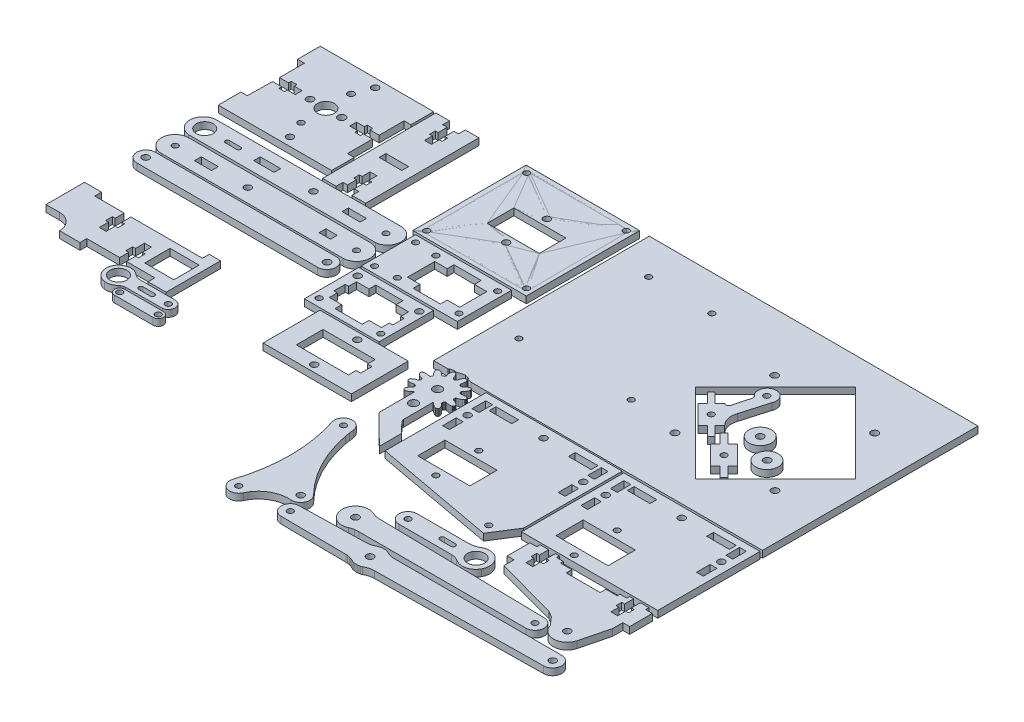
SolidWorks part; units mm, degrees
ref_plane "Front Plane" through (0, 0, 0) normal (0, 0, 1) x (1, 0, 0)
ref_plane "Top Plane" through (0, 0, 0) normal (0, 1, 0) x (1, 0, 0)
ref_plane "Right Plane" through (0, 0, 0) normal (1, 0, 0) x (0, 0, -1)
other "Graphic1"
other "Graphic (Closed) -1"
other "Graphic (Closed) -2"
other "Graphic (Closed) -3"
other "Graphic (Closed) -4"
other "Graphic (Closed) -5"
other "Graphic (Closed) -6"
other "Graphic (Closed) -7"
other "Graphic (Closed) -8"
other "Graphic (Closed) -9"
other "Graphic (Closed) -10"
other "Graphic (Closed) -11"
other "Graphic (Closed) -12"
other "Graphic (Closed) -13"
other "Graphic (Closed) -14"
other "Graphic (Closed) -15"
other "Graphic (Closed) -16"
other "Graphic (Closed) -17"
other "Graphic (Closed) -18"
other "Graphic (Closed) -19"
other "Graphic (Closed) -20"
other "Graphic (Closed) -21"
other "Graphic (Closed) -22"
other "Graphic (Closed) -23"
other "Graphic (Closed) -24"
other "Graphic (Closed) -25"
other "Graphic (Closed) -26"
other "Graphic (Closed) -27"
other "Graphic (Closed) -28"
other "Graphic (Closed) -29"
other "Graphic (Closed) -30"
other "Graphic (Closed) -31"
other "Graphic (Closed) -32"
other "Graphic (Closed) -33"
other "Graphic (Closed) -34"
other "Graphic (Closed) -35"
other "Graphic (Closed) -36"
other "Graphic (Closed) -37"
sketch "Sketch3" plane through (0, 0, 0) normal (0, 1, 0) x (1, 0, 0)
  line L0 (0, 0) -> (50, 0)
  line L1 (50, 0) -> (50, -10)
  line L2 (50, -10) -> (47, -10)
  line L3 (47, -10) -> (47, -21)
  line L4 (47, -21) -> (43, -21)
  line L5 (43, -21) -> (43, -19.8259)
  line L6 (43, -19.8259) -> (40.5, -19.75)
  line L7 (40.5, -19.75) -> (40.5, -21)
  line L8 (40.5, -21) -> (37, -21)
  line L9 (37, -21) -> (37, -24)
  line L10 (37, -24) -> (40.5, -24)
  line L11 (40.5, -24) -> (40.5, -25.275)
  line L12 (40.5, -25.275) -> (43, -25.25)
  line L13 (43, -25.25) -> (43, -24)
  line L14 (43, -24) -> (47, -24)
  line L15 (47, -24) -> (47, -35)
  line L16 (47, -35) -> (50, -35)
  line L17 (50, -35) -> (50, -45)
  line L18 (50, -45) -> (0, -45)
  line L19 (0, -45) -> (0, -35)
  line L20 (0, -35) -> (2.8271, -35)
  line L21 (3, -24) -> (7, -24)
  line L22 (7, -24) -> (7, -25.275)
  line L23 (7, -25.275) -> (9.5, -25.1741)
  line L24 (9.5, -25.1741) -> (9.5, -24)
  line L25 (9.5, -24) -> (13, -24)
  line L26 (13, -24) -> (13, -21)
  line L27 (13, -21) -> (9.5, -21)
  line L28 (9.5, -21) -> (9.5, -19.8259)
  line L29 (9.5, -19.8259) -> (7, -19.8259)
  line L30 (7, -19.8259) -> (7, -21)
  line L31 (7, -21) -> (3, -21)
  line L32 (3, -21) -> (3, -10)
  line L33 (3, -10) -> (0, -10)
  line L34 (0, -10) -> (0, 0)
  line L35 (2.8271, -35) -> (3, -24)
  circle A0 centre (25, -22.5) radius 3.75
  circle A1 centre (18, -22.5) radius 1.5333
  circle A2 centre (24.9904, -11.4176) radius 1.4239
  circle A3 centre (31.9506, -22.5119) radius 1.6482
  circle A4 centre (28, -3.75) radius 1.5
  circle A5 centre (25, -33.4941) radius 1.3524
  circle A6 centre (27.9864, -41.3394) radius 1.4891
  dimension "D1" = 10
extrude "Boss-Extrude1" add sketch "Sketch3" along normal blind 3
sketch "Sketch5" plane through (0, 0, 0) normal (0, 1, 0) x (1, 0, 0)
  line L0 (57, 0) -> (57, -3)
  line L1 (57, -3) -> (59, -3)
  line L2 (59, -3) -> (59, -7)
  line L3 (59, -7) -> (57.75, -7)
  line L4 (57.75, -7) -> (57.75, -9.5)
  line L5 (57.75, -9.5) -> (59, -9.5)
  line L6 (59, -9.5) -> (59, -13)
  line L7 (59, -13) -> (62, -13)
  line L8 (62, -13) -> (62, -9.5)
  line L9 (62, -9.5) -> (63.25, -9.5)
  line L10 (63.25, -9.5) -> (63.25, -7)
  line L11 (63.25, -7) -> (62, -7)
  line L12 (62, -7) -> (62, -3)
  line L13 (62, -3) -> (64, -3)
  line L14 (64, -3) -> (64, 0)
  line L15 (64, 0) -> (70, 0)
  line L16 (70, 0) -> (70, -50)
  line L17 (70, -50) -> (64, -50)
  line L18 (64, -50) -> (64, -47)
  line L19 (64, -47) -> (62, -47)
  line L20 (62, -47) -> (62, -43)
  line L21 (62, -43) -> (63.25, -43)
  line L22 (63.25, -43) -> (63.25, -40.5)
  line L23 (63.25, -40.5) -> (62, -40.5)
  line L24 (62, -40.5) -> (62, -37)
  line L25 (62, -37) -> (59, -37)
  line L26 (59, -37) -> (59, -40.5)
  line L27 (59, -40.5) -> (57.75, -40.5)
  line L28 (57.75, -40.5) -> (57.75, -43)
  line L29 (57.75, -43) -> (59, -43)
  line L30 (59, -43) -> (59, -47)
  line L31 (59, -47) -> (57, -47)
  line L32 (57, -47) -> (57, -50)
  line L33 (57, -50) -> (51, -50)
  line L34 (51, -50) -> (51, 0)
  line L35 (51, 0) -> (57, 0)
  line L36 (55.5, -26.5) -> (65.5, -26.5)
  line L37 (65.5, -26.5) -> (65.5, -29.5)
  line L38 (65.5, -29.5) -> (55.5, -29.5)
  line L39 (55.5, -29.5) -> (55.5, -26.5)
extrude "Boss-Extrude2" add sketch "Sketch5" along normal blind 3 separate body
sketch "Sketch8" plane through (0, 0, 0) normal (0, 1, 0) x (1, 0, 0)
  line L0 (104.5, -19.1) -> (127.5, -19.1)
  line L1 (127.5, -19.1) -> (127.5, -30.9)
  line L2 (127.5, -30.9) -> (104.5, -30.9)
  line L3 (104.5, -30.9) -> (104.5, -19.1)
  line L4 (90.8358, -0.1468) -> (90.8358, -49.9799)
  line L5 (90.8358, -49.9799) -> (140.8298, -49.9799)
  line L6 (140.8298, -49.9799) -> (140.8298, 0)
  line L7 (140.8298, 0) -> (90.8358, -0.1468)
  circle A0 centre (116, -16) radius 1.5
  circle A1 centre (116, -34) radius 1.5
  circle A2 centre (138, -3) radius 1.3
  circle A3 centre (94, -47) radius 1.3
  circle A4 centre (93.9724, -2.8702) radius 1.295
  circle A5 centre (138, -47) radius 1.3
extrude "Boss-Extrude3" add sketch "Sketch8" along normal blind 3 separate body
sketch "Sketch14" plane through (0, 0, 0) normal (0, 1, 0) x (1, 0, 0)
  line L0 (234.1407, -55.7028) -> (232.0194, -57.8241)
  line L1 (232.0194, -57.8241) -> (236.262, -62.0667)
  line L2 (236.262, -62.0667) -> (234.565, -63.7638)
  line L3 (234.565, -63.7638) -> (230.3223, -59.5211)
  line L4 (230.3223, -59.5211) -> (228.201, -61.6425)
  line L5 (228.201, -61.6425) -> (219.7157, -53.1572)
  line L6 (219.7157, -53.1572) -> (221.837, -51.0359)
  line L7 (221.837, -51.0359) -> (217.5944, -46.7932)
  line L8 (217.5944, -46.7932) -> (219.2915, -45.0962)
  line L9 (219.2915, -45.0962) -> (223.5341, -49.3388)
  line L10 (223.5341, -49.3388) -> (225.6554, -47.2175)
  line L11 (227.9135, -46.2821) -> (229.7551, -39.4354)
  line L12 (232.4436, -48.2782) -> (235.8289, -36.5593)
  line L14 (229.7551, -39.4354) -> (229.7551, -38.1986)
  line L15 (244.0402, -59.9454) -> (252.5255, -68.4307)
  line L16 (252.5255, -68.4307) -> (250.4042, -70.552)
  line L17 (250.4042, -70.552) -> (254.6468, -74.7947)
  line L18 (254.6468, -74.7947) -> (252.9497, -76.4917)
  line L19 (252.9497, -76.4917) -> (248.7071, -72.2491)
  line L20 (248.7071, -72.2491) -> (246.5858, -74.3704)
  line L21 (246.5858, -74.3704) -> (238.1005, -65.8851)
  line L22 (238.1005, -65.8851) -> (240.2218, -63.7638)
  line L23 (240.2218, -63.7638) -> (235.9792, -59.5211)
  line L24 (235.9792, -59.5211) -> (237.6762, -57.8241)
  line L25 (237.6762, -57.8241) -> (241.9189, -62.0667)
  line L26 (241.9189, -62.0667) -> (244.0402, -59.9454)
  arc A0 (225.6554, -47.2175) -> (227.9135, -46.2821) centre (226.5908, -46.2821) ccw
  arc A3 (234.1407, -55.7028) -> (232.4436, -48.2782) centre (239.2043, -50.6391) cw
  circle A4 centre (232.1046, -35.1115) radius 1.3
  arc A5 (235.8289, -36.5593) -> (229.7551, -38.1986) centre (232.1294, -34.9238) ccw
  circle A6 centre (226.9282, -54.43) radius 1.3
  circle A7 centre (246.1553, -52.0356) radius 1.55
  circle A8 centre (246.1553, -52.0356) radius 5
  circle A9 centre (256.8229, -59.6467) radius 1.55
  circle A10 centre (256.7818, -59.6877) radius 5.004
  circle A11 centre (245.313, -67.1579) radius 1.3
extrude "Boss-Extrude5" add sketch "Sketch14" along normal blind 3 separate body
sketch "Sketch10" plane through (0, 0, 0) normal (0, 1, 0) x (1, 0, 0)
  line L0 (145.1554, 0) -> (145.1554, -95.0975)
  line L1 (145.1554, -95.0975) -> (290.1997, -95.0975)
  line L2 (290.1997, -95.0975) -> (290.1997, 0)
  line L3 (290.1997, 0) -> (145.1554, 0)
  line L4 (248.1731, -12.0958) -> (283.3826, -47.3054)
  line L5 (283.3826, -47.3054) -> (248.1731, -82.5149)
  line L6 (248.1731, -82.5149) -> (212.9636, -47.3054)
  line L7 (212.9636, -47.3054) -> (248.1731, -12.0958)
  circle A0 centre (226.0091, -25.54) radius 1.5505
  circle A1 centre (188.5027, -15.7221) radius 1.3002
  circle A2 centre (160.6027, -15.7221) radius 1.3002
  circle A3 centre (155.5, -67.875) radius 1.2905
  circle A4 centre (203.7027, -66.5221) radius 1.3002
  circle A5 centre (226, -69.5) radius 1.55
  circle A7 centre (270.1244, -25.4918) radius 1.5641
  circle A8 centre (270.1073, -69.4833) radius 1.5564
extrude "Boss-Extrude4" add sketch "Sketch10" along normal blind 3 separate body
sketch "Sketch16" plane through (0, 0, 0) normal (0, 1, 0) x (1, 0, 0)
  line L0 (229.9704, -96.0247) -> (290.0442, -96.0247)
  line L1 (290.0442, -96.0247) -> (290.0442, -141.1373)
  line L2 (290.0442, -141.1373) -> (229.9704, -141.1373)
  line L3 (229.9704, -141.1373) -> (229.9704, -96.0247)
  line L5 (237.5, -99) -> (247.5, -99)
  line L6 (237.5, -99) -> (237.5, -102)
  line L7 (237.5, -102) -> (247.5, -102)
  line L8 (247.5, -99) -> (247.5, -102)
  line L9 (272.5, -99) -> (282.5, -99)
  line L10 (272.5, -99) -> (272.5, -102)
  line L11 (272.5, -102) -> (282.5, -102)
  line L12 (282.5, -99) -> (282.5, -102)
  line L13 (284, -99) -> (287, -99)
  line L14 (284, -99) -> (284, -105)
  line L15 (284, -105) -> (287, -105)
  line L16 (287, -99) -> (287, -105)
  line L17 (284, -112) -> (287, -112)
  line L18 (284, -112) -> (284, -118)
  line L19 (284, -118) -> (287, -118)
  line L20 (287, -112) -> (287, -118)
  line L21 (239, -123) -> (262, -123)
  line L22 (239, -123) -> (239, -135)
  line L23 (239, -135) -> (262, -135)
  line L24 (262, -123) -> (262, -135)
  line L25 (233, -112) -> (236, -112)
  line L26 (233, -112) -> (233, -118)
  line L27 (233, -118) -> (236, -118)
  line L28 (236, -112) -> (236, -118)
  line L29 (233, -99) -> (236, -99)
  line L30 (233, -99) -> (233, -105)
  line L31 (233, -105) -> (236, -105)
  line L32 (236, -99) -> (236, -105)
  circle A0 centre (260, -100.5) radius 1.5
  circle A1 centre (250.5, -119.5) radius 1.3
  circle A2 centre (250.5, -138.4651) radius 1.2962
  circle A3 centre (285.5, -108.5) radius 1.5
  circle A4 centre (234.5, -108.5) radius 1.5
extrude "Boss-Extrude6" add sketch "Sketch16" along normal blind 3 separate body
sketch "Sketch17" plane through (0, 0, 0) normal (0, 1, 0) x (1, 0, 0)
  line L0 (290, -153.5) -> (287, -153.5)
  line L2 (287, -157.9581) -> (283.8136, -170.4839)
  line L3 (272.1099, -170.6397) -> (269.0056, -167.0206)
  line L4 (269.0056, -167.0206) -> (266.2659, -165.3797)
  line L5 (266.2659, -165.3797) -> (239, -158)
  line L6 (239, -158) -> (239, -153.5)
  line L7 (239, -153.5) -> (236, -153.5)
  line L8 (236, -153.5) -> (236, -143.5)
  line L9 (236, -143.5) -> (239, -143.5)
  line L10 (239, -143.5) -> (239, -142)
  line L11 (239, -142) -> (242.75, -142)
  line L12 (242.75, -142) -> (242.75, -146)
  line L13 (242.75, -146) -> (241.5, -146)
  line L14 (241.5, -146) -> (241.5, -148.5)
  line L15 (241.5, -148.5) -> (242.75, -148.5)
  line L16 (242.75, -148.5) -> (242.75, -152)
  line L17 (242.75, -152) -> (245.75, -152)
  line L18 (245.75, -152) -> (245.75, -148.5)
  line L19 (245.75, -148.5) -> (247, -148.5)
  line L20 (247, -148.5) -> (247, -146)
  line L21 (247, -146) -> (245.75, -146)
  line L22 (245.75, -146) -> (245.75, -142)
  line L23 (245.75, -142) -> (247.5, -142)
  line L24 (247.5, -142) -> (247.5, -143.25)
  line L25 (247.5, -143.25) -> (250.5, -143.25)
  line L26 (250.5, -143.25) -> (250.5, -144.5)
  line L27 (250.5, -144.5) -> (255.5, -144.5)
  line L28 (255.5, -144.5) -> (255.5, -147)
  line L29 (255.5, -147) -> (270.5, -147)
  line L30 (270.5, -147) -> (270.5, -144.5)
  line L31 (270.5, -144.5) -> (275.5, -144.5)
  line L32 (275.5, -144.5) -> (275.5, -143.25)
  line L33 (275.5, -143.25) -> (278.5, -143.25)
  line L34 (278.5, -143.25) -> (278.5, -142)
  line L35 (278.5, -142) -> (280.25, -142)
  line L36 (280.25, -142) -> (280.25, -146)
  line L37 (280.25, -146) -> (279, -146)
  line L38 (279, -146) -> (279, -148.5)
  line L39 (279, -148.5) -> (280.25, -148.5)
  line L40 (280.25, -148.5) -> (280.25, -152)
  line L41 (280.25, -152) -> (283.25, -152)
  line L42 (283.25, -152) -> (283.25, -148.5)
  line L43 (283.25, -148.5) -> (284.5, -148.5)
  line L44 (284.5, -148.5) -> (284.5, -146)
  line L45 (284.5, -146) -> (283.25, -146)
  line L46 (283.25, -146) -> (283.25, -142)
  line L47 (283.25, -142) -> (287, -142)
  line L48 (287, -142) -> (287, -143.4733)
  line L49 (287, -143.4733) -> (290, -143.5)
  line L50 (290, -143.5) -> (290, -153.5)
  line L51 (287, -153.5) -> (287, -157.9581)
  arc A0 (283.8136, -170.4839) -> (272.1099, -170.6397) centre (277.9408, -168.9899) cw
  circle A1 centre (278, -169) radius 1.5
sketch "Sketch18" plane through (0, 0, 0) normal (0, 1, 0) x (1, 0, 0)
  line L0 (200, -157.2561) -> (222.4609, -157.2561)
  line L1 (200, -165.2561) -> (223.0953, -165.2916)
  line L2 (215.0106, -161.2805) -> (219.919, -161.2805) construction
  line L3 (215.0106, -160.2674) -> (219.919, -160.2674)
  line L4 (215.0106, -162.2937) -> (219.919, -162.2937)
  line L5 (267.8316, -169.0008) -> (193.5528, -167.5414)
  line L6 (267.753, -177) -> (194.0263, -176.9878)
  line L7 (170.9118, -180.2312) -> (199.7222, -179.5779)
  line L8 (212.2547, -179.474) -> (286, -179.474)
  line L9 (286.0526, -187.4737) -> (212.3137, -188.4434)
  line L10 (199.7809, -188.5043) -> (170.9644, -188.2299)
  line L11 (154.2411, -141.4201) -> (154.5835, -143.5068)
  line L12 (154.2411, -141.4201) -> (153.9775, -139.3221)
  line L13 (20.5, -107) -> (7.5, -107)
  line L18 (13, -128) -> (22, -128)
  line L19 (22, -128) -> (22, -125)
  line L20 (22, -125) -> (36.5, -125)
  line L21 (36.5, -125) -> (36.5, -121)
  line L22 (36.5, -121) -> (35.25, -121)
  line L23 (35.25, -121) -> (35.25, -118)
  line L24 (35.25, -118) -> (36.5, -118)
  line L25 (36.5, -118) -> (36.5, -114)
  line L26 (36.5, -114) -> (39.5, -114)
  line L27 (39.5, -114) -> (39.5, -118)
  line L28 (39.5, -118) -> (40.75, -118)
  line L29 (40.75, -118) -> (40.75, -121)
  line L30 (40.75, -121) -> (39.5, -121)
  line L31 (39.5, -121) -> (39.5, -125)
  line L32 (39.5, -125) -> (52, -125)
  line L33 (52, -125) -> (52, -128)
  line L34 (52, -128) -> (60, -128)
  line L35 (60, -128) -> (60, -104)
  line L36 (60, -104) -> (55, -104)
  line L37 (55, -104) -> (55, -107)
  line L38 (55, -107) -> (23.5, -107)
  line L39 (23.5, -107) -> (23.5, -111)
  line L40 (23.5, -111) -> (24.75, -111)
  line L41 (24.75, -111) -> (24.75, -114)
  line L42 (24.75, -114) -> (23.5, -114)
  line L43 (23.5, -114) -> (23.5, -118)
  line L44 (23.5, -118) -> (20.5, -118)
  line L45 (20.5, -118) -> (20.5, -114)
  line L46 (20.5, -114) -> (19.25, -114)
  line L47 (19.25, -114) -> (19.25, -111)
  line L48 (19.25, -111) -> (20.5, -111)
  line L49 (20.5, -111) -> (20.5, -107)
  line L50 (7.5, -107) -> (7.5, -104)
  line L51 (0, -104) -> (0, -121)
  line L52 (64.9545, -129) -> (49.7552, -129)
  line L53 (44.1121, -110.3569) -> (56.9411, -110.3569)
  line L54 (44.1121, -110.3569) -> (44.1121, -121.5466)
  line L55 (44.1121, -121.5466) -> (56.9411, -121.5466)
  line L56 (56.9411, -110.3569) -> (56.9411, -121.5466)
  line L57 (65.4238, -134.9631) -> (49.1694, -135.0344)
  line L58 (49.1694, -135.0344) -> (48.5917, -135.1373)
  line L59 (52.8796, -132) -> (57.9387, -132) construction
  line L60 (52.8796, -131.0268) -> (57.9387, -131.0268)
  line L61 (52.8796, -132.9732) -> (57.9387, -132.9732)
  line L62 (49.7552, -136) -> (66.7552, -136)
  line L63 (66.7552, -140.5) -> (49.7552, -140.5)
  line L64 (113, -54) -> (125, -54)
  line L65 (93.0108, -51.0177) -> (135.4404, -51.0177)
  line L66 (93.0108, -51.0177) -> (93.0108, -74.9726)
  line L67 (93.0108, -74.9726) -> (135.4404, -74.9726)
  line L68 (135.4404, -51.0177) -> (135.4404, -74.9726)
  line L69 (125, -54) -> (125, -57)
  line L70 (125, -57) -> (130.5, -57)
  line L71 (130.5, -57) -> (130.5, -69)
  line L72 (130.5, -69) -> (125, -69)
  line L73 (125, -69) -> (125, -72)
  line L74 (125, -72) -> (113, -72)
  line L75 (113, -72) -> (113, -69)
  line L76 (113, -69) -> (107.5, -69)
  line L77 (107.5, -69) -> (107.5, -57)
  line L78 (107.5, -57) -> (113, -57)
  line L79 (113, -57) -> (113, -54)
  line L80 (103.5, -79) -> (115.5, -79)
  line L81 (93.0108, -76.0168) -> (125.9342, -76.0168)
  line L82 (93.0108, -76.0168) -> (93.0108, -100.0006)
  line L83 (93.0108, -100.0006) -> (125.9342, -100.0006)
  line L84 (125.9342, -76.0168) -> (125.9342, -100.0006)
  line L85 (115.5, -79) -> (115.5, -82)
  line L86 (115.5, -82) -> (121, -82)
  line L87 (121, -82) -> (121, -85.5)
  line L88 (121, -85.5) -> (122.5, -85.5)
  line L89 (122.5, -85.5) -> (122.5, -90.5)
  line L90 (122.5, -90.5) -> (121, -90.5)
  line L91 (121, -90.5) -> (121, -94)
  line L92 (121, -94) -> (115.5, -94)
  line L93 (115.5, -94) -> (115.5, -97)
  line L94 (115.5, -97) -> (103.5, -97)
  line L95 (103.5, -97) -> (103.5, -94)
  line L96 (103.5, -94) -> (98, -94)
  line L97 (98, -94) -> (98, -90.5)
  line L98 (98, -90.5) -> (96.5, -90.5)
  line L99 (96.5, -90.5) -> (96.5, -85.5)
  line L100 (96.5, -85.5) -> (98, -85.5)
  line L101 (98, -85.5) -> (98, -82)
  line L102 (98, -82) -> (103.5, -82)
  line L103 (103.5, -82) -> (103.5, -79)
  line L104 (5.3282, -51.0377) -> (86.6718, -51.0377)
  line L105 (4.6649, -62.8496) -> (87.3351, -62.8496)
  line L106 (86, -64) -> (6, -64)
  line L107 (68, -55.6) -> (76, -55.6)
  line L108 (68, -55.6) -> (68, -58.4)
  line L109 (68, -58.4) -> (76, -58.4)
  line L110 (76, -55.6) -> (76, -58.4)
  line L111 (29, -55.5) -> (38, -55.5)
  line L112 (29, -55.5) -> (29, -58.4)
  line L113 (29, -58.4) -> (38, -58.4)
  line L114 (38, -55.5) -> (38, -58.4)
  line L115 (5.9093, -76.0168) -> (86, -76)
  line L116 (86, -76.0168) -> (86, -76)
  line L117 (4.1133, -80.9665) -> (83.9018, -80.9665) construction
  line L118 (16, -68.5) -> (23.5, -68.5)
  line L119 (16, -68.5) -> (16, -71.5)
  line L120 (16, -71.5) -> (23.5, -71.5)
  line L121 (23.5, -68.5) -> (23.5, -71.5)
  line L122 (71, -68.5) -> (76, -68.5)
  line L123 (71, -68.5) -> (71, -71.5)
  line L124 (71, -71.5) -> (76, -71.5)
  line L125 (76, -68.5) -> (76, -71.5)
  line L126 (4.1133, -76.8805) -> (83.9018, -76.8805)
  line L127 (4.1133, -85.0526) -> (83.9018, -85.0526)
  line L128 (108.8263, -107.6) -> (131.8263, -107.6)
  line L129 (100.7991, -100.9119) -> (139.7148, -100.9119)
  line L130 (100.7991, -100.9119) -> (100.7991, -125.9873)
  line L131 (100.7991, -125.9873) -> (139.7148, -125.9873)
  line L132 (139.7148, -100.9119) -> (139.7148, -125.9873)
  line L133 (131.8263, -107.6) -> (131.8263, -111)
  line L134 (131.8263, -111) -> (133.8263, -111)
  line L135 (133.8263, -111) -> (133.8263, -116)
  line L136 (133.8263, -116) -> (131.8263, -116)
  line L137 (131.8263, -116) -> (131.8263, -119.4)
  line L138 (131.8263, -119.4) -> (108.8263, -119.4)
  line L139 (108.8263, -119.4) -> (108.8263, -107.6)
  line L140 (0, -121) -> (6, -121)
  line L141 (7.5, -104) -> (0, -104)
  line L142 (16, -56.9739) -> (20.9727, -56.9739) construction
  line L143 (16, -56.0886) -> (20.9727, -56.0886)
  line L144 (16, -57.8592) -> (20.9727, -57.8592)
  arc A0 (222.4609, -157.2561) -> (227.7188, -155.7067) centre (222.4609, -147.5601) ccw
  arc A1 (227.7188, -155.7067) -> (235.3049, -164.0722) centre (229.9663, -161.2909) cw
  arc A2 (235.3049, -164.0722) -> (226.342, -166.1299) centre (229.9463, -161.2805) cw
  arc A3 (223.0953, -165.2916) -> (226.342, -166.1299) centre (223.0849, -172.0381) cw
  arc A4 (215.0106, -160.2674) -> (215.0106, -162.2937) centre (215.0106, -161.2805) ccw
  arc A5 (219.919, -162.2937) -> (219.919, -160.2674) centre (219.919, -161.2805) ccw
  circle A6 centre (200, -161.2561) radius 1.3
  circle A7 centre (230, -161.2561) radius 3.75
  arc A8 (186.9656, -166.2666) -> (181.7853, -172.6293) centre (187.5568, -172.0381) ccw
  arc A9 (181.7853, -172.6293) -> (184.9077, -177.4946) centre (188.1536, -171.9769) ccw
  arc A10 (184.9077, -177.4946) -> (190.201, -177.6938) centre (187.7392, -172.6813) ccw
  arc A11 (190.201, -177.6938) -> (192.1236, -177.1124) centre (192.9314, -183.2534) cw
  arc A12 (192.1236, -177.1124) -> (194.0263, -176.9878) centre (194.0263, -191.5764) cw
  arc A13 (186.9656, -166.2666) -> (190.927, -167.0433) centre (187.6714, -173.1572) cw
  arc A14 (190.927, -167.0433) -> (192.219, -167.4028) centre (192.3848, -164.3057) ccw
  arc A15 (192.219, -167.4028) -> (193.5528, -167.5414) centre (191.503, -180.7801) cw
  arc A16 (267.8316, -169.0008) -> (267.753, -177) centre (267.753, -173) cw
  circle A17 centre (267.753, -173) radius 1.3
  circle A18 centre (187.7569, -172.2142) radius 1.55
  arc A19 (200, -165.2561) -> (200, -157.2561) centre (200, -161.2561) cw
  arc A20 (199.7222, -179.5779) -> (203.8045, -178.4168) centre (199.5311, -171.1489) ccw
  arc A21 (203.8045, -178.4168) -> (204.4002, -178.2177) centre (204.5718, -179.7217) cw
  arc A22 (204.4002, -178.2177) -> (205.0136, -178.0819) centre (204.0583, -175.22) ccw
  arc A23 (205.0136, -178.0819) -> (205.6377, -178.0111) centre (205.4924, -179.5162) cw
  arc A24 (205.6377, -178.0111) -> (206.2659, -178.0058) centre (205.9266, -175.0192) ccw
  arc A25 (206.2659, -178.0058) -> (206.8911, -178.0663) centre (206.4363, -179.5056) cw
  arc A26 (206.8911, -178.0663) -> (207.5066, -178.1918) centre (207.7947, -175.2067) ccw
  arc A27 (207.5066, -178.1918) -> (208.1056, -178.381) centre (207.3617, -179.6935) cw
  arc A28 (208.1056, -178.381) -> (208.6816, -178.6317) centre (209.5813, -175.7776) ccw
  arc A29 (208.6816, -178.6317) -> (209.3587, -178.9315) centre (207.6809, -181.8063) cw
  arc A30 (209.3587, -178.9315) -> (210.0607, -179.1673) centre (210.2789, -177.3547) ccw
  arc A31 (210.0607, -179.1673) -> (210.7815, -179.3372) centre (209.6635, -182.4664) cw
  arc A32 (210.7815, -179.3372) -> (211.5149, -179.4397) centre (211.3956, -177.6184) ccw
  arc A33 (211.5149, -179.4397) -> (212.2547, -179.474) centre (211.732, -182.753) cw
  arc A34 (286, -179.474) -> (286.0526, -187.4737) centre (286, -183.474) cw
  arc A35 (212.3137, -188.4434) -> (208.1793, -189.5909) centre (212.4244, -196.8642) ccw
  arc A36 (208.1793, -189.5909) -> (207.5829, -189.7879) centre (207.4173, -188.2854) cw
  arc A37 (207.5829, -189.7879) -> (206.9691, -189.9215) centre (207.9125, -192.7788) ccw
  arc A38 (206.9691, -189.9215) -> (206.3447, -189.9902) centre (206.4952, -188.4861) cw
  arc A39 (206.3447, -189.9902) -> (205.7165, -189.9932) centre (206.0449, -192.9866) ccw
  arc A40 (205.7165, -189.9932) -> (205.0915, -189.9305) centre (205.5516, -188.4903) cw
  arc A41 (205.0915, -189.9305) -> (204.4764, -189.8029) centre (204.1768, -192.7934) ccw
  arc A42 (204.4764, -189.8029) -> (203.8781, -189.6116) centre (204.6268, -188.3011) cw
  arc A43 (203.8781, -189.6116) -> (203.303, -189.3588) centre (202.3904, -192.2154) ccw
  arc A44 (203.303, -189.3588) -> (202.6358, -189.0602) centre (204.3017, -186.2325) cw
  arc A45 (202.6358, -189.0602) -> (201.9442, -188.8238) centre (201.7158, -190.6217) ccw
  arc A46 (201.9442, -188.8238) -> (201.2338, -188.6514) centre (202.3572, -185.5722) cw
  arc A47 (201.2338, -188.6514) -> (200.5107, -188.5446) centre (200.6131, -190.3529) ccw
  arc A48 (200.5107, -188.5446) -> (199.7809, -188.5043) centre (200.3254, -185.2716) cw
  arc A49 (170.9644, -188.2299) -> (170.9118, -180.2312) centre (171.0025, -184.2301) cw
  circle A50 centre (171.0025, -184.2301) radius 1.3
  circle A51 centre (206.0017, -184) radius 1.55
  circle A52 centre (286, -183.474) radius 1.5
  arc A53 (153.9775, -139.3221) -> (146.1703, -141.0234) centre (149.9873, -139.7752) ccw
  arc A54 (146.1703, -141.0234) -> (146.2067, -184.7308) centre (79.1711, -162.9328) cw
  arc A55 (146.2067, -184.7308) -> (153.6593, -187.6155) centre (150.0123, -185.9683) ccw
  arc A56 (153.6593, -187.6155) -> (166.8709, -179.8286) centre (165.789, -193.0941) cw
  arc A57 (166.8709, -179.8286) -> (170.0608, -173.0188) centre (167.1971, -175.8294) ccw
  arc A58 (170.0608, -173.0188) -> (154.5835, -143.5068) centre (211.2304, -132.6133) cw
  circle A59 centre (167.23, -175.8448) radius 1.5
  circle A60 centre (150, -186) radius 1.3
  circle A61 centre (150, -139.7458) radius 1.3
  arc A62 (6, -121) -> (13, -128) centre (6, -128) cw
  arc A63 (49.7552, -129) -> (45.9906, -127.414) centre (49.7552, -123.7391) cw
  arc A64 (45.9906, -127.414) -> (42.2211, -137.4509) centre (43.0137, -132.0223) ccw
  arc A65 (42.2211, -137.4509) -> (46.9854, -135.8373) centre (43.021, -131.9724) ccw
  arc A66 (46.9854, -135.8373) -> (47.4921, -135.5415) centre (47.7737, -136.6058) cw
  arc A67 (47.4921, -135.5415) -> (48.5917, -135.1373) centre (45.8898, -129.4847) ccw
  arc A68 (64.9545, -129) -> (65.4238, -134.9631) centre (64.9545, -132) cw
  arc A69 (52.8796, -131.0268) -> (52.8796, -132.9732) centre (52.8796, -132) ccw
  arc A70 (57.9387, -132.9732) -> (57.9387, -131.0268) centre (57.9387, -132) ccw
  circle A71 centre (42.9545, -132) radius 3.75
  circle A72 centre (64.9545, -132) radius 1.3
  arc A73 (66.7552, -136) -> (66.7552, -140.5) centre (66.7552, -138.25) cw
  arc A74 (49.7552, -140.5) -> (49.7552, -136) centre (49.7552, -138.25) cw
  circle A75 centre (49.7552, -138.25) radius 1.3
  circle A76 centre (66.7552, -138.25) radius 1.3
  circle A77 centre (105.5, -71.5) radius 1.2989
  circle A78 centre (96, -72.05) radius 1.3
  circle A79 centre (105.5, -54.5) radius 1.2989
  circle A80 centre (96, -53.95) radius 1.3
  circle A81 centre (132.7, -71.5) radius 1.2989
  circle A82 centre (132.7045, -54.4632) radius 1.3039
  circle A83 centre (95.9955, -79.5127) radius 1.5016
  circle A84 centre (96, -96.5) radius 1.2989
  circle A85 centre (123.2065, -96.4827) radius 1.3013
  circle A86 centre (123.2, -79.5) radius 1.5
  arc A88 (5.3282, -51.0377) -> (4.6649, -62.8496) centre (5.3282, -56.9623) ccw
  arc A89 (86.6718, -51.0377) -> (87.3351, -62.8496) centre (86.6718, -56.9623) cw
  arc A90 (6, -64) -> (5.9093, -76.0168) centre (5.9547, -70.0084) ccw
  arc A91 (86, -64) -> (86, -76.0168) centre (86, -70.0084) cw
  circle A92 centre (86, -70) radius 1.3
  circle A93 centre (38, -70) radius 1.5
  circle A94 centre (6, -70) radius 1.3
  arc A95 (4.1133, -76.8805) -> (4.1133, -85.0526) centre (4.1133, -80.9665) ccw
  arc A96 (83.9018, -85.0526) -> (83.9018, -76.8805) centre (83.9018, -80.9665) ccw
  circle A97 centre (4, -81) radius 1.55
  circle A98 centre (84, -81) radius 1.55
  circle A99 centre (120.3263, -104) radius 1.5
  circle A100 centre (120.3263, -123) radius 1.5
  circle A101 centre (6.0077, -56.9739) radius 3.7501
  circle A102 centre (86, -57) radius 1.3
  circle A103 centre (54, -57) radius 1.5
  arc A104 (16, -56.0886) -> (16, -57.8592) centre (16, -56.9739) ccw
  arc A105 (20.9727, -57.8592) -> (20.9727, -56.0886) centre (20.9727, -56.9739) ccw
  point P18 (217.4648, -161.2805)
  point P319 (55.4091, -132)
  point P520 (44.0075, -80.9665)
  point P575 (18.4864, -56.9739)
extrude "Boss-Extrude7" add sketch "Sketch18" along normal blind 3 separate body
extrude "Boss-Extrude8" add sketch "Sketch17" along normal blind 3 separate body
sketch "Sketch23" plane through (0, 0, 0) normal (0, 1, 0) x (1, 0, 0)
  line L0 (168.929, -95.7598) -> (228.9845, -95.7598)
  line L1 (228.9845, -95.7598) -> (228.9845, -139.2514)
  line L2 (228.9845, -139.2514) -> (222.1369, -150.0781)
  line L3 (222.1369, -150.0781) -> (168.929, -140.2693)
  line L4 (168.929, -140.2693) -> (168.929, -95.7598)
  line L6 (176.5, -99) -> (186.5, -99)
  line L7 (176.5, -99) -> (176.5, -102)
  line L8 (176.5, -102) -> (186.5, -102)
  line L9 (186.5, -99) -> (186.5, -102)
  line L10 (172, -99) -> (175, -99)
  line L11 (172, -99) -> (172, -105)
  line L12 (172, -105) -> (175, -105)
  line L13 (175, -99) -> (175, -105)
  line L14 (172, -112) -> (175, -112)
  line L15 (172, -112) -> (172, -118)
  line L16 (172, -118) -> (175, -118)
  line L17 (175, -112) -> (175, -118)
  line L18 (178, -123) -> (201, -123)
  line L19 (178, -123) -> (178, -135)
  line L20 (178, -135) -> (201, -135)
  line L21 (201, -123) -> (201, -135)
  line L22 (211.5, -99) -> (221.5, -99)
  line L23 (211.5, -99) -> (211.5, -102)
  line L24 (211.5, -102) -> (221.5, -102)
  line L25 (221.5, -99) -> (221.5, -102)
  line L26 (223, -99) -> (226, -99)
  line L27 (223, -99) -> (223, -105)
  line L28 (223, -105) -> (226, -105)
  line L29 (226, -99) -> (226, -105)
  line L30 (223, -112) -> (226, -112)
  line L31 (223, -112) -> (223, -118)
  line L32 (223, -118) -> (226, -118)
  line L33 (226, -112) -> (226, -118)
  circle A0 centre (224.5132, -108.4789) radius 1.503
  circle A1 centre (220.252, -145.9059) radius 1.2998
  circle A2 centre (189.4997, -138.5014) radius 1.2998
  circle A3 centre (189.518, -119.5731) radius 1.3112
  circle A4 centre (173.5, -108.5) radius 1.5
  circle A5 centre (199, -100.5) radius 1.5
extrude "Boss-Extrude9" add sketch "Sketch23" along normal blind 3 separate body
sketch "Sketch24" plane through (0, 0, 0) normal (0, 1, 0) x (1, 0, 0)
  line L0 (146.2955, -102.258) -> (146.7341, -102.514)
  line L1 (146.7341, -102.514) -> (146.7341, -102.8467)
  line L2 (146.7341, -102.8467) -> (146.8825, -103.1532)
  line L3 (146.8825, -103.1532) -> (147.0178, -103.3192)
  line L4 (147.0178, -103.3192) -> (147.4553, -103.675)
  line L5 (147.4553, -103.675) -> (147.9381, -103.9665)
  line L6 (147.9381, -103.9665) -> (148.4567, -104.1881)
  line L7 (148.4567, -104.1881) -> (149.001, -104.3353)
  line L8 (149.001, -104.3353) -> (149.2258, -104.4129)
  line L9 (149.2258, -104.4129) -> (149.421, -104.5485)
  line L10 (149.421, -104.5485) -> (149.572, -104.7322)
  line L11 (149.572, -104.7322) -> (149.6674, -104.9499)
  line L12 (149.6674, -104.9499) -> (149.6674, -105.0865)
  line L13 (149.6674, -105.0865) -> (149.6674, -105.3593)
  line L14 (149.6674, -105.3593) -> (149.6674, -105.5747)
  line L15 (149.6674, -105.5747) -> (149.421, -105.8223)
  line L16 (149.421, -105.8223) -> (149.1134, -105.9571)
  line L17 (149.1134, -105.9571) -> (148.844, -106.0752)
  line L18 (148.844, -106.0752) -> (148.4567, -106.1828)
  line L19 (148.4567, -106.1828) -> (147.9381, -106.4044)
  line L20 (147.9381, -106.4044) -> (147.4553, -106.7233)
  line L21 (147.4553, -106.7233) -> (147.0178, -107.0517)
  line L22 (147.0178, -107.0517) -> (146.8825, -107.2176)
  line L23 (146.8825, -107.2176) -> (146.7646, -107.6252)
  line L24 (146.7646, -107.6252) -> (146.7905, -107.8378)
  line L25 (146.7905, -107.8378) -> (146.3875, -107.8869)
  line L26 (146.3875, -107.8869) -> (145.4004, -104.3353)
  line L27 (145.4004, -104.3353) -> (145.8736, -102.6993)
  line L28 (145.8736, -102.6993) -> (146.2955, -102.258)
sketch "Sketch27" plane through (0, 0, 0) normal (0, 1, 0) x (1, 0, 0)
  circle A0 centre (156.9333, -105.1571) radius 10.5421
extrude "Boss-Extrude13" add sketch "Sketch27" along normal blind 3
extrude "Cut-Extrude5" cut sketch "Sketch24" against normal blind 1 and the other way through all contours L28 L0 L1 L2 L3 L4 L5 L6 L7 L8 L9 L10 L11 L12 L13 L14 L15 L16 L17 L18 L19 L20 L21 L22 L23 L24 L25 L26 L27
pattern_circular "CirPattern1" count 12 over 360 about axis through (156.9333, 0, 105.1571) along (0, 1, 0) of "Cut-Extrude5"
sketch "Sketch28" plane through (0, 0, 0) normal (0, 1, 0) x (1, 0, 0)
  line L0 (165.8974, -139.8225) -> (165.8974, -130.1259)
  line L1 (165.8974, -130.1259) -> (161.277, -125.2548)
  line L2 (161.277, -125.2548) -> (160.9869, -124.3621)
  line L3 (160.9869, -124.3621) -> (160.9278, -111.2408)
  line L4 (160.9278, -111.2408) -> (152.8846, -111.3197)
  line L5 (152.8846, -111.3197) -> (152.8846, -126.9951)
  line L6 (152.8846, -126.9951) -> (165.8974, -139.8225)
  circle A1 centre (156.959, -115.8083) radius 1.9
  dimension "D2" = 3.8
extrude "Boss-Extrude14" add sketch "Sketch28" along normal blind 3
sketch "Sketch29" plane through (0, 0, 0) normal (0, 1, 0) x (1, 0, 0)
  circle A2 centre (156.9168, -105.1372) radius 1.9
  dimension "D2" = 3.8
extrude "Cut-Extrude6" cut sketch "Sketch29" along normal blind 3
sketch "Sketch30" plane through (0, 0, 0) normal (0, 1, 0) x (1, 0, 0)
  line L1 (90.8633, 0) -> (140.916, 0)
  line L2 (90.8633, 0) -> (90.8633, -49.9171)
  line L3 (90.8633, -49.9171) -> (140.916, -49.9171)
  line L4 (140.916, 0) -> (140.916, -49.9171)
  line L5 (104.4662, -30.8277) -> (127.6137, -30.8277)
  line L6 (104.4662, -30.8277) -> (104.4662, -19.0284)
  line L7 (104.4662, -19.0284) -> (127.6137, -19.0284)
  line L8 (127.6137, -30.8277) -> (127.6137, -19.0284)
  circle A0 centre (93.9975, -3.0077) radius 1.296
  circle A1 centre (116.0016, -16.0119) radius 1.4983
  circle A2 centre (138.0041, -2.9965) radius 1.3
  circle A3 centre (115.9987, -34.0018) radius 1.4936
  circle A4 centre (138.0025, -46.9935) radius 1.2981
  circle A5 centre (93.9993, -47.0026) radius 1.2959
sketch "Sketch31" plane through (0, 0, 0) normal (0, 1, 0) x (1, 0, 0)
  line L0 (212.4675, -47.3025) -> (248.0572, -82.8922)
  line L1 (144.9487, 0) -> (290.1151, 0)
  line L2 (144.9487, 0) -> (144.9487, -94.7312)
  line L3 (144.9487, -94.7312) -> (290.1151, -94.7312)
  line L4 (290.1151, 0) -> (290.1151, -94.7312)
  line L5 (248.0572, -82.8922) -> (283.5209, -47.4285)
  line L6 (283.5209, -47.4285) -> (247.9312, -11.8388)
  line L7 (247.9312, -11.8388) -> (212.4675, -47.3025)
  circle A4 centre (226, -25.5) radius 1.55
  circle A5 centre (188.5, -15.7) radius 1.3
  circle A6 centre (160.6, -15.7) radius 1.3
  circle A7 centre (155.5, -67.8) radius 1.3
  circle A8 centre (203.7, -66.5) radius 1.3
  circle A9 centre (226, -69.5) radius 1.55
  circle A10 centre (270, -69.5) radius 1.55
  circle A11 centre (270, -25.5) radius 1.55
extrude "Boss-Extrude15" add sketch "Sketch30" along normal blind 3 separate body
